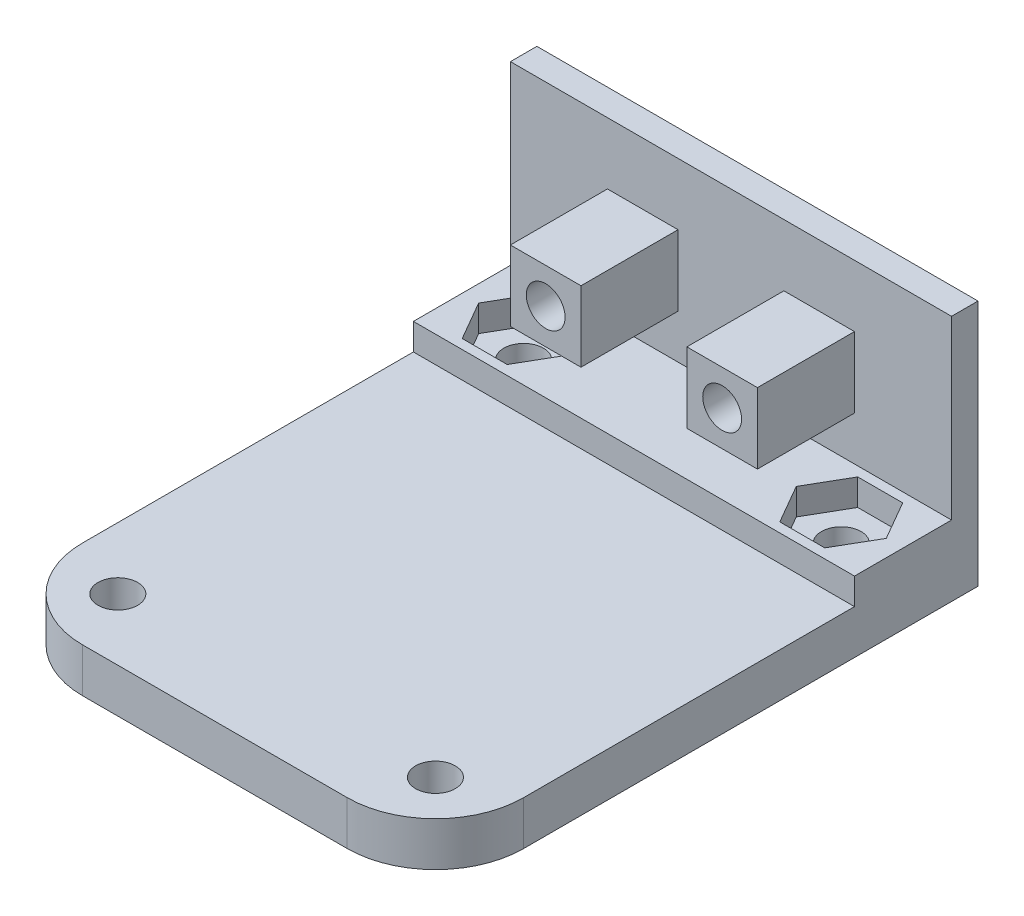
SolidWorks part; units mm, degrees
ref_plane "Front Plane" through (0, 0, 0) normal (0, 0, 1) x (1, 0, 0)
ref_plane "Top Plane" through (0, 0, 0) normal (0, 1, 0) x (1, 0, 0)
ref_plane "Right Plane" through (0, 0, 0) normal (1, 0, 0) x (0, 0, -1)
sketch "Sketch1" plane through (0, 0, 0) normal (0, 0, 1) x (1, 0, 0)
  line L1 (-25, 16.5) -> (25, 16.5)
  line L2 (-25, 16.5) -> (-25, -16.5)
  line L3 (-25, -16.5) -> (25, -16.5)
  line L4 (25, 16.5) -> (25, -16.5)
  line L5 (-25, 16.5) -> (25, -16.5) construction
  line L6 (-25, -16.5) -> (25, 16.5) construction
  point P0 (0, 0)
  dimension "D1" = 33
  dimension "D2" = 50
extrude "Boss-Extrude1" add sketch "Sketch1" along normal blind 3 contours L2 L3 L4 L1
sketch "Sketch2" plane through (0, 0, 3) normal (0, 0, 1) x (1, 0, 0)
  line L0 (25, 16.5) -> (25, -16.5) construction
  line L1 (-25, -16.5) -> (25, -16.5)
  line L2 (-25, -16.5) -> (-25, -11.5)
  line L3 (-25, -11.5) -> (25, -11.5)
  line L4 (25, -16.5) -> (25, -11.5)
  dimension "D1" = 5
extrude "Boss-Extrude2" add sketch "Sketch2" along normal blind 58.5
sketch "Sketch3" plane through (0, -11.5, 0) normal (0, 1, 0) x (1, 0, 0)
  line L0 (-25, -51.5) -> (-25, -61.5)
  line L1 (-25, -61.5) -> (-15, -61.5)
  line L2 (15, -61.5) -> (25, -61.5)
  line L3 (25, -61.5) -> (25, -51.5)
  arc A1 (15, -61.5) -> (25, -51.5) centre (15, -51.5) ccw construction
  arc A2 (15, -61.5) -> (25, -51.5) centre (15, -51.5) ccw
  arc A3 (-25, -51.5) -> (-15, -61.5) centre (-15, -51.5) ccw construction
  arc A4 (-25, -51.5) -> (-15, -61.5) centre (-15, -51.5) ccw
  circle A5 centre (-18, -54.5) radius 2.2479 construction
  circle A6 centre (-18, -54.5) radius 2.2479
  circle A7 centre (18, -54.5) radius 2.2479 construction
  circle A8 centre (18, -54.5) radius 2.2479
  circle A9 centre (-18, -8.5) radius 2.2479 construction
  circle A10 centre (-18, -8.5) radius 2.2479
  circle A11 centre (18, -8.5) radius 2.2479 construction
  circle A12 centre (18, -8.5) radius 2.2479
extrude "Cut-Extrude1" cut sketch "Sketch3" against normal up to surface (5 mm away) up to face at (0, -16.5, 30.75)
sketch "Sketch4" plane through (0, 0, 3) normal (0, 0, 1) x (1, 0, 0)
  line L5 (-14.0006, 4.5) -> (-6.0006, 4.5)
  line L6 (-14.0006, 4.5) -> (-14.0006, -3.5)
  line L7 (-14.0006, -3.5) -> (-6.0006, -3.5)
  line L8 (-6.0006, 4.5) -> (-6.0006, -3.5)
  line L9 (-14.0006, 4.5) -> (-6.0006, -3.5) construction
  line L10 (-14.0006, -3.5) -> (-6.0006, 4.5) construction
  line L11 (5.9994, 4.5) -> (13.9994, 4.5)
  line L12 (5.9994, 4.5) -> (5.9994, -3.5)
  line L13 (5.9994, -3.5) -> (13.9994, -3.5)
  line L14 (13.9994, 4.5) -> (13.9994, -3.5)
  line L15 (5.9994, 4.5) -> (13.9994, -3.5) construction
  line L16 (5.9994, -3.5) -> (13.9994, 4.5) construction
  circle A0 centre (-10.0006, 0.5) radius 2.2 construction
  circle A1 centre (-10.0006, 0.5) radius 2.2
  circle A2 centre (9.9994, 0.5) radius 2.2 construction
  circle A3 centre (9.9994, 0.5) radius 2.2
  dimension "D1" = 8
extrude "Boss-Extrude3" add sketch "Sketch4" along normal blind 11
sketch "Sketch5" plane through (0, 0, 14) normal (0, 0, 1) x (1, 0, 0)
  circle A0 centre (9.9994, 0.5) radius 2.2 construction
  circle A1 centre (9.9994, 0.5) radius 2.2
  circle A2 centre (-10.0006, 0.5) radius 2.2 construction
  circle A3 centre (-10.0006, 0.5) radius 2.2
extrude "Cut-Extrude2" cut sketch "Sketch5" against normal up to surface (14 mm away) up to face at (0, 0, 0)
sketch "Sketch6" plane through (0, 0, 3) normal (0, 0, 1) x (1, 0, 0)
  line L0 (25, 16.5) -> (25, -11.5) construction
  line L1 (-25, 16.5) -> (25, 16.5)
  line L2 (-25, 16.5) -> (-25, 11.5)
  line L3 (-25, 11.5) -> (25, 11.5)
  line L4 (25, 16.5) -> (25, 11.5)
  dimension "D1" = 5
extrude "Cut-Extrude3" cut sketch "Sketch6" against normal up to surface (3 mm away) up to face at (7.7994, 0.5, 0)
sketch "Sketch7" plane through (0, -11.5, 0) normal (0, 1, 0) x (1, 0, 0)
  line L0 (25, -51.5) -> (25, -3) construction
  line L1 (-25, -3) -> (25, -3)
  line L2 (-25, -3) -> (-25, -14)
  line L3 (-25, -14) -> (25, -14)
  line L4 (25, -3) -> (25, -14)
  dimension "D1" = 11
extrude "Boss-Extrude4" add sketch "Sketch7" along normal blind 3
sketch "Sketch8" plane through (0, -8.5, 0) normal (0, 1, 0) x (1, 0, 0)
  line L0 (25, -3) -> (-25, -3) construction
  line L1 (-15.45, -4.0833) -> (-20.55, -4.0833)
  line L2 (-20.55, -4.0833) -> (-23.1, -8.5)
  line L3 (-23.1, -8.5) -> (-20.55, -12.9167)
  line L4 (-20.55, -12.9167) -> (-15.45, -12.9167)
  line L5 (-15.45, -12.9167) -> (-12.9, -8.5)
  line L6 (-12.9, -8.5) -> (-15.45, -4.0833)
  line L8 (0, -15.4) -> (0, 15.4) construction
  line L9 (12.9, -8.5) -> (15.45, -4.0833)
  line L10 (15.45, -12.9167) -> (12.9, -8.5)
  line L11 (20.55, -12.9167) -> (15.45, -12.9167)
  line L12 (23.1, -8.5) -> (20.55, -12.9167)
  line L13 (20.55, -4.0833) -> (23.1, -8.5)
  line L14 (15.45, -4.0833) -> (20.55, -4.0833)
  circle A0 centre (-18, -8.5) radius 2.2479 construction
  circle A1 centre (-18, -8.5) radius 2.2479 construction
  circle A2 centre (-18, -8.5) radius 4.4167 construction
  circle A3 centre (18, -8.5) radius 4.4167 construction
  circle A4 centre (18, -8.5) radius 2.2479 construction
  dimension "D1" = 5.1
extrude "Cut-Extrude4" cut sketch "Sketch8" against normal blind 3
